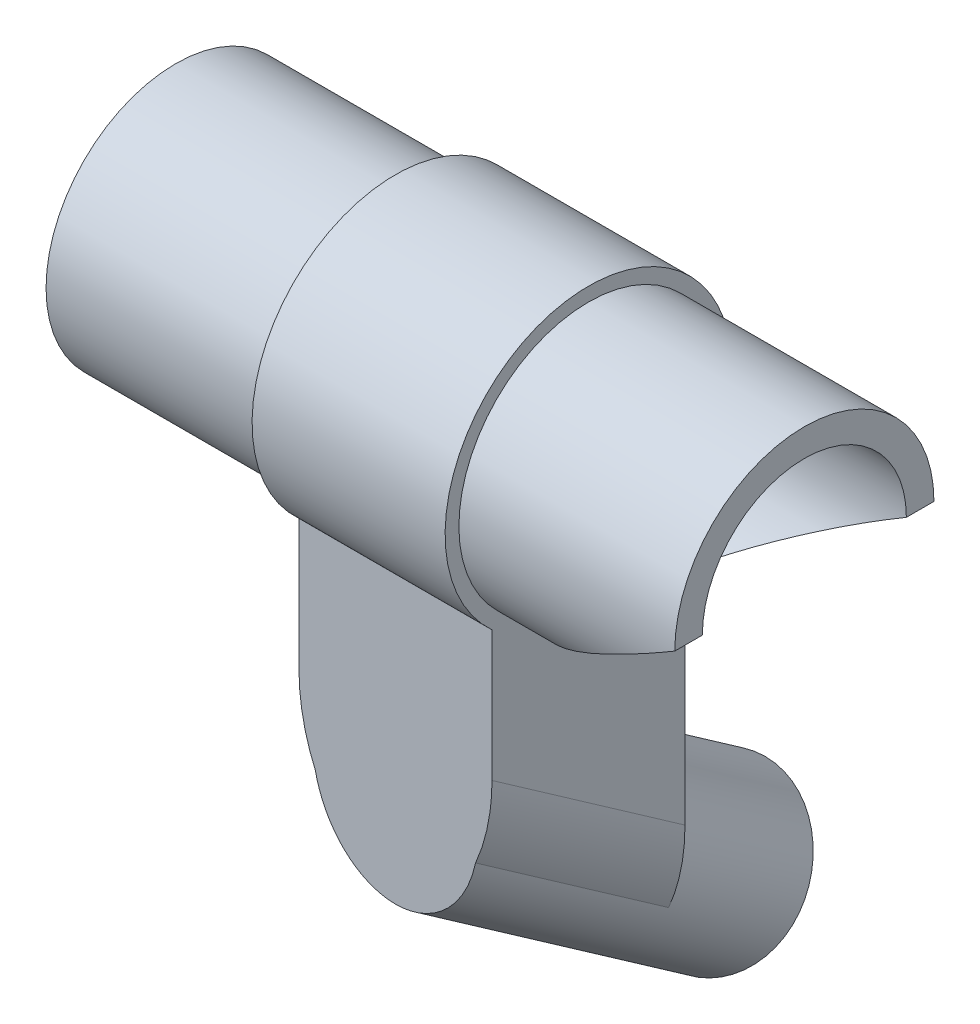
SolidWorks part; units mm, degrees
ref_plane "Alzado" through (0, 0, 0) normal (0, 0, 1) x (1, 0, 0)
ref_plane "Planta" through (0, 0, 0) normal (0, 1, 0) x (1, 0, 0)
ref_plane "Vista lateral" through (0, 0, 0) normal (1, 0, 0) x (0, 0, -1)
sketch "Croquis1" plane through (0, 0, 0) normal (1, 0, 0) x (0, 0, -1)
  circle A0 centre (0, 0) radius 18.5
  circle A1 centre (0, 0) radius 23.5
  dimension "D1" = 37
  dimension "D2" = 5
extrude "Saliente-Extruir1" add sketch "Croquis1" along normal blind 114
sketch "Croquis2" plane through (0, 0, 0) normal (-1, 0, 0) x (0, 0, 1)
  circle A0 centre (0, 0) radius 5.375
  circle A1 centre (0, 0) radius 23.5
  circle A2 centre (-12.4762, 6.3517) radius 1.25
  circle A3 centre (-6.3517, -12.4762) radius 1.25
  circle A4 centre (12.4762, -6.3517) radius 1.25
  circle A5 centre (6.3517, 12.4762) radius 1.25
  dimension "D1" = 2.5
  dimension "D2" = 47
extrude "Saliente-Extruir2" add sketch "Croquis2" against normal blind 5
sketch "Croquis4" plane through (0, 0, 0) normal (0, 0, 1) x (1, 0, 0)
  line L0 (114, 0) -> (74, -23.5)
  line L1 (0, -23.5) -> (114, -23.5) construction
  line L2 (74, -23.5) -> (114, -23.5)
  line L3 (114, -23.5) -> (114, 0)
  dimension "D1" = 23.5
  dimension "D2" = 40
extrude "Cortar-Extruir1" cut sketch "Croquis4" against normal mid plane 47
sketch "Croquis6" plane through (5, 0, 0) normal (1, 0, 0) x (0, 0, -1)
  circle A0 centre (0, 0) radius 11.5
  dimension "D1" = 23
extrude "Cortar-Extruir2" cut sketch "Croquis6" against normal blind 2.5
sketch "Croquis17" plane through (0, 0, 0) normal (0, 1, 0) x (1, 0, 0)
  line L1 (39.8579, 17.5) -> (74.8579, 17.5)
  line L2 (39.8579, 17.5) -> (39.8579, -17.5)
  line L3 (39.8579, -17.5) -> (74.8579, -17.5)
  line L4 (74.8579, 17.5) -> (74.8579, -17.5)
  line L5 (39.8579, 17.5) -> (74.8579, -17.5) construction
  line L6 (39.8579, -17.5) -> (74.8579, 17.5) construction
  dimension "D1" = 35
extrude "Saliente-Extruir3" add sketch "Croquis17" against normal blind 65
sketch3d "Croquis3D4"
  line L0 (57.3579, -65, 0) -> (57.3579, -93.6788, -40.9576) construction
  line L2 (57.3579, -65, 0) -> (57.3579, -65, -44.525) construction
  line L3 (74.8579, -65, -17.5) -> (39.8579, -65, 17.5) construction
  line L4 (57.3579, -65, 0) -> (65.365, -65, 0) construction
  point P2 (57.3579, -65, 0)
  dimension "D1" = 35
  dimension "D2" = 50
  dimension "D3" = 90
ref_plane "Plano4" through (57.3579, -93.6788, -40.9576) normal (0, -0.5736, -0.8192) x (-1, 0, 0)
sketch "Croquis18" plane through (57.3579, -93.6788, -40.9576) normal (0, -0.5736, -0.8192) x (-1, 0, 0)
  circle A0 centre (0, 0) radius 15
  circle A1 centre (0, 0) radius 12.5
  dimension "D1" = 25
  dimension "D2" = 30
extrude "Saliente-Extruir4" add sketch "Croquis18" against normal blind 70
ref_plane "Plano5" through (57.3579, 0, 0) normal (1, 0, 0) x (0, 0, -1)
sketch "Croquis26" plane through (0, -65, 0) normal (0, -1, 0) x (1, 0, 0)
  line L0 (39.8579, 17.5) -> (74.8579, 17.5)
  line L1 (74.8579, 17.5) -> (74.8579, -17.5)
  line L2 (74.8579, -17.5) -> (39.8579, -17.5)
  line L3 (39.8579, -17.5) -> (39.8579, 17.5)
extrude "Saliente-Extruir8" add sketch "Croquis26" along normal blind 40
sketch "Croquis23" plane through (0, -50.0632, -71.4976) normal (0, -0.5736, -0.8192) x (-1, 0.0003, -0.0002)
  line L0 (-72.3771, -53.2242) -> (-106.2851, -53.2242)
  line L1 (-42.3771, -53.2242) -> (-8.469, -53.2242)
  arc A0 (-72.3771, -53.2242) -> (-42.3771, -53.2242) centre (-57.3771, -53.2242) ccw
  arc A1 (-106.2851, -53.2242) -> (-8.469, -53.2242) centre (-57.3771, -53.2242) ccw
  circle A2 centre (-57.3771, -53.2242) radius 15 construction
  point P1 (-57.3771, -68.2242)
extrude "Cortar-Extruir4" cut sketch "Croquis23" against normal through all
sketch "Croquis25" plane through (39.8579, 0, 0) normal (-1, 0, 0) x (0, 0, 1)
  line L0 (17.5, -37.7048) -> (17.5, -82.1788)
  line L1 (17.5, -52.7387) -> (17.5, -15.6844) construction
  line L2 (17.5, -82.1788) -> (34.9062, -82.1788)
  line L3 (34.9062, -82.1788) -> (34.9062, -37.7048)
  line L4 (34.9062, -37.7048) -> (17.5, -37.7048)
chamfer "Chaflán1" distance 5 angle 45 2 edges at (72.3579, -65.0066, 0) (42.3579, -64.9934, 0)
sketch "Croquis27" plane through (39.8579, 0, 0) normal (-1, 0, 0) x (0, 0, 1)
  circle A0 centre (0, 0) radius 26
  dimension "D1" = 52
extrude "Saliente-Extruir9" add sketch "Croquis27" against normal blind 35
sketch "Croquis28" plane through (74.8579, 0, 0) normal (1, 0, 0) x (0, 0, -1)
  circle A0 centre (0, 0) radius 18.5
extrude "Cortar-Extruir7" cut sketch "Croquis28" against normal blind 35
extrude "Cortar-Extruir8" cut sketch "Croquis25" against normal blind 35
fillet "Redondeo7" radius 25 2 edges at (74.8579, -66.7707, 0) (39.8579, -66.7563, 0)
